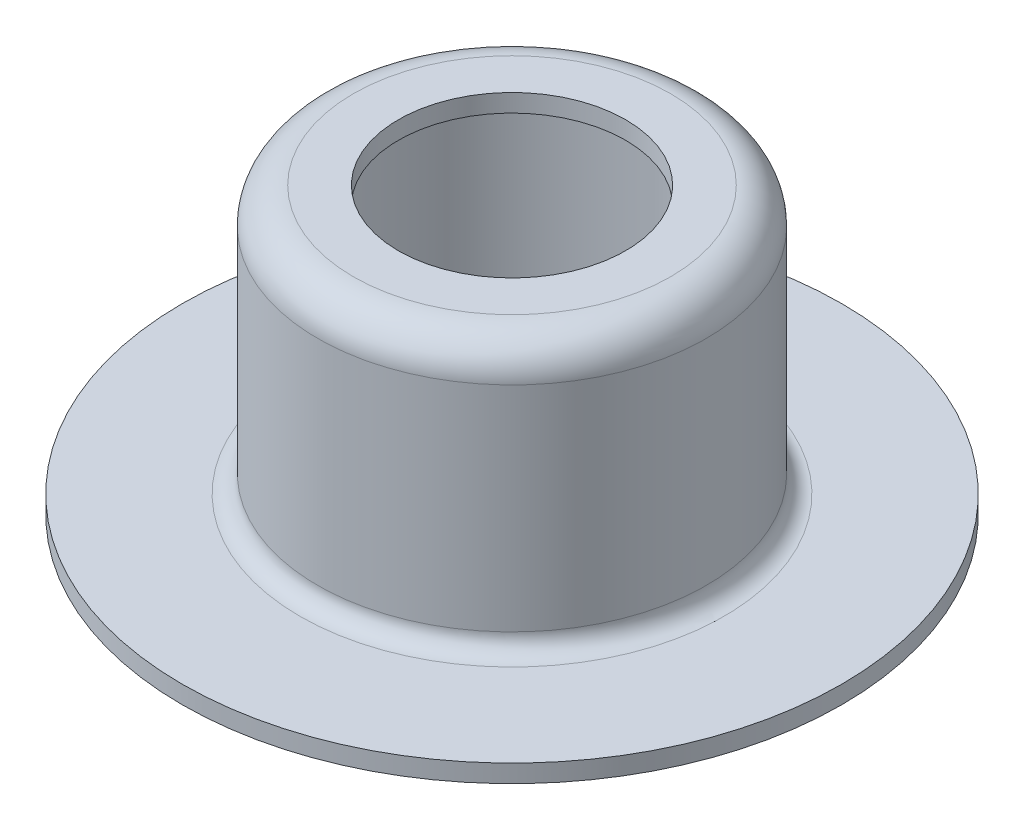
SolidWorks part; units mm, degrees
material "AISI 316 Stainless Steel Sheet (SS)"
ref_plane "Front Plane" through (0, 0, 0) normal (0, 0, 1) x (1, 0, 0)
ref_plane "Top Plane" through (0, 0, 0) normal (0, 1, 0) x (1, 0, 0)
ref_plane "Right Plane" through (0, 0, 0) normal (1, 0, 0) x (0, 0, -1)
sketch "Sketch1" plane through (0, 0, 0) normal (0, 0, 1) x (1, 0, 0)
  line L0 (0, 0) -> (0, 70.8619) construction
  line L1 (-18.5, 0) -> (-10.9, 0)
  line L2 (-8.9, 2) -> (-8.9, 14)
  line L3 (-7.9, 15) -> (-6.375, 15)
  line L4 (-6.375, 15) -> (-6.375, 16)
  line L5 (-6.375, 16) -> (-8.9, 16)
  line L6 (-10.9, 14) -> (-10.9, 2)
  line L7 (-11.9, 1) -> (-18.5, 1)
  line L8 (-18.5, 1) -> (-18.5, 0)
  arc A0 (-10.9, 2) -> (-11.9, 1) centre (-11.9, 2) cw
  arc A1 (-8.9, 14) -> (-7.9, 15) centre (-7.9, 14) cw
  arc A2 (-10.9, 0) -> (-8.9, 2) centre (-10.9, 2) ccw
  arc A3 (-8.9, 16) -> (-10.9, 14) centre (-8.9, 14) ccw
  point P18 (-8.9, 15)
  point P21 (-8.9, 0)
  dimension "D8" = 1
  dimension "D9" = 2
  dimension "D1" = 8.9
  dimension "D2" = 1
  dimension "D3" = 15
  dimension "D4" = 6.375
  dimension "D5" = 2
  dimension "D6" = 1
  dimension "D7" = 18.5
revolve "Revolve1" add sketch "Sketch1" angle 360 about L0
equation "\"D1@Sketch1\"=(17.75+0.05)/2"
equation "\"D4@Sketch1\"=(16.75-4)/2"
equation "\"D7@Sketch1\"=37/2"
